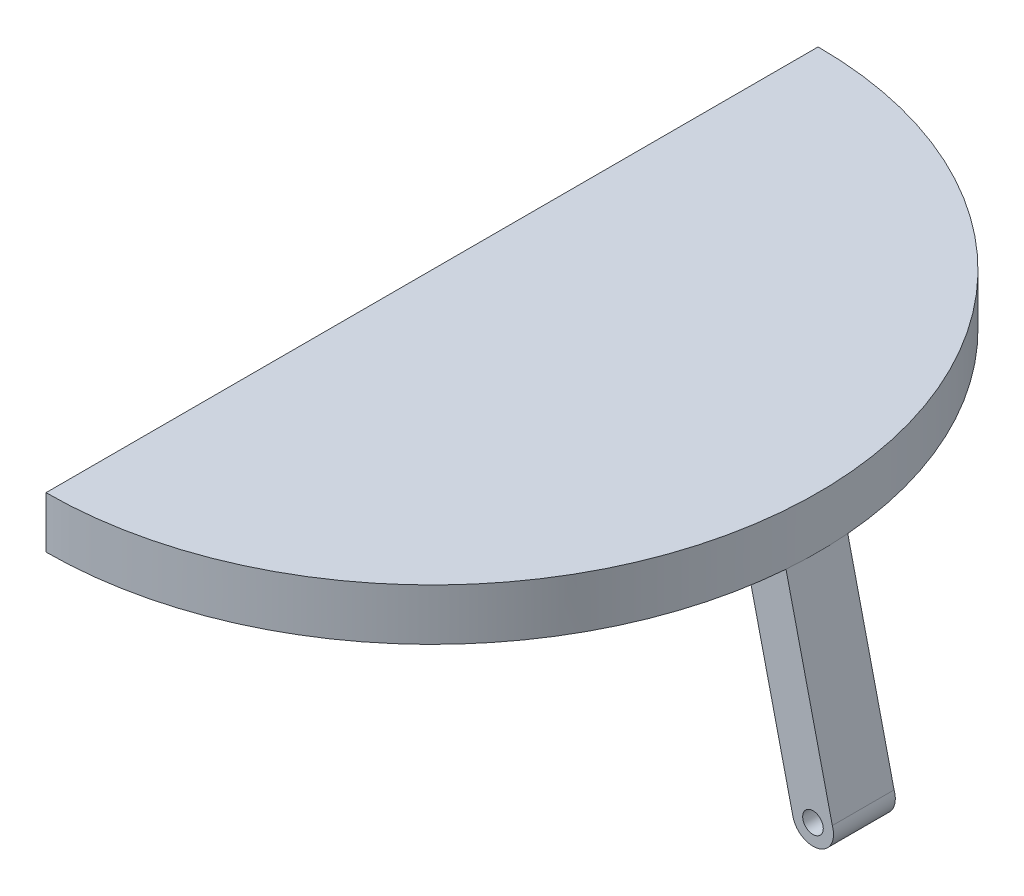
SolidWorks part; units mm, degrees
ref_plane "Ebene vorne" through (0, 0, 0) normal (0, 0, 1) x (1, 0, 0)
ref_plane "Ebene oben" through (0, 0, 0) normal (0, 1, 0) x (1, 0, 0)
ref_plane "Ebene rechts" through (0, 0, 0) normal (1, 0, 0) x (0, 0, -1)
sketch "Skizze1" plane through (0, 0, 0) normal (0, 1, 0) x (1, 0, 0)
  line L0 (0, 0) -> (0, -75)
  arc A0 (0, -75) -> (0, 0) centre (0, -37.5) ccw
  dimension "D1" = 75
extrude "Aufsatz-Linear austragen1" add sketch "Skizze1" along normal blind 5
sketch "Skizze10" plane through (0, 0, 0) normal (0, -1, 0) x (1, 0, 0)
  line L0 (37.3798, 40.5) -> (37.3798, 34.5)
  line L1 (0, 0) -> (0, 75) construction
  arc A0 (0, 0) -> (0, 75) centre (0, 37.5) ccw construction
  dimension "D1" = 6
ref_plane "Ebene1" through (37.3798, 0, 40.5) normal (0, 0, 1) x (1, 0, 0)
sketch "Skizze12" plane through (37.3798, 0, 40.5) normal (0, 0, 1) x (1, 0, 0)
  line L0 (0, 0) -> (4.4992, -19.315)
  line L2 (0.6723, -20.4537) -> (-4.0921, 0)
  line L3 (-4.0921, 0) -> (0, 0)
  line L4 (-37.3798, 8.8878) -> (-37.3798, -28.7638) construction
  line L5 (2.6202, -15.4311) -> (2.6202, -25.351) construction
  line L6 (4.832, -20) -> (14.1192, -20) construction
  arc A0 (0.6723, -20.4537) -> (4.4992, -19.315) centre (2.6202, -20) ccw
  dimension "D1" = 40
  dimension "D2" = 2
  dimension "D3" = 20
extrude "Aufsatz-Linear austragen2" add sketch "Skizze12" against normal up to vertex (6 mm away) contours L0 A0 L2 L3 up to point (37.3798, 0, 34.5)
sketch "Skizze13" plane through (37.3798, 0, 40.5) normal (0, 0, 1) x (1, 0, 0)
  circle A4 centre (2.6202, -20) radius 1
  arc A5 (0.6723, -20.4537) -> (4.4992, -19.315) centre (2.6202, -20) ccw construction
extrude "Schnitt-Linear austragen1" cut sketch "Skizze13" against normal up to surface (6 mm away) up to face at (37.8009, -10.4503, 34.5)
